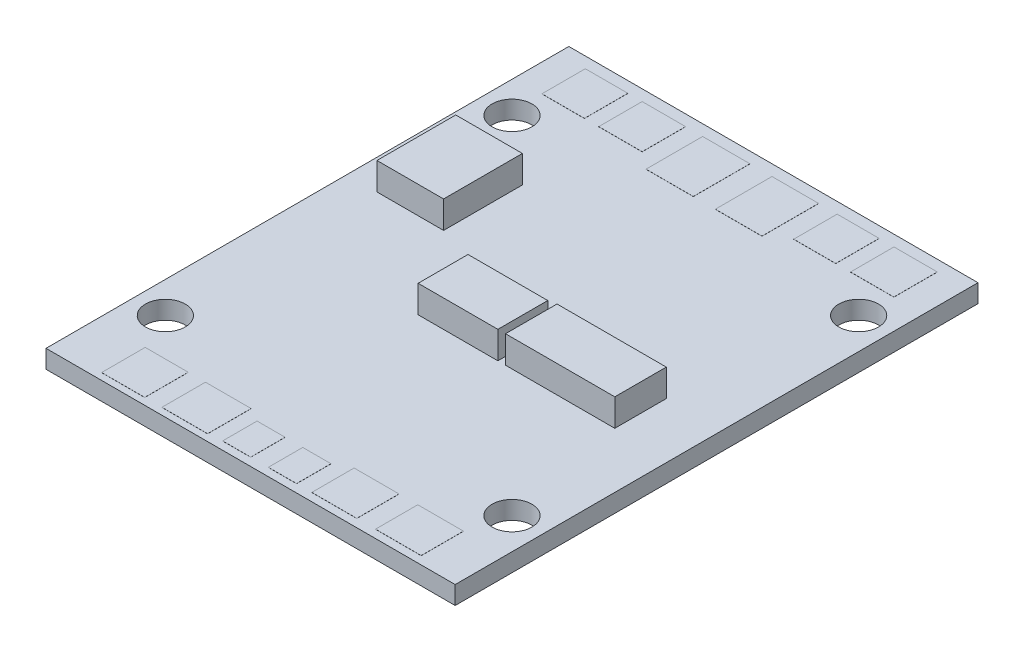
SolidWorks part; units mm, degrees
ref_plane "Front Plane" through (0, 0, 0) normal (0, 0, 1) x (1, 0, 0)
ref_plane "Top Plane" through (0, 0, 0) normal (0, 1, 0) x (1, 0, 0)
ref_plane "Right Plane" through (0, 0, 0) normal (1, 0, 0) x (0, 0, -1)
sketch "Sketch1" plane through (0, 0, 0) normal (0, 1, 0) x (1, 0, 0)
  line L0 (0, 18) -> (0, -18) construction
  line L1 (-18, 23) -> (18, 23)
  line L2 (-18, 23) -> (-18, -23)
  line L3 (-18, -23) -> (18, -23)
  line L4 (18, 23) -> (18, -23)
  line L5 (-18, 23) -> (18, -23) construction
  line L6 (-18, -23) -> (18, 23) construction
  line L7 (18, -18) -> (-18, -18)
  line L8 (18, -18) -> (18, 18)
  line L9 (18, 18) -> (-18, 18)
  line L10 (-18, -18) -> (-18, 18)
  line L11 (18, -18) -> (-18, 18) construction
  line L12 (18, 18) -> (-18, -18) construction
  line L13 (-18, 0) -> (18, 0) construction
  circle A0 centre (-15.25, 15.25) radius 1.75
  circle A1 centre (15.25, 15.25) radius 1.75
  circle A2 centre (-15.25, -15.25) radius 1.75
  circle A3 centre (15.25, -15.25) radius 1.75
  point P0 (0, 0)
  point P6 (0, 0)
  dimension "D3" = 3.5
  dimension "D1" = 46
  dimension "D2" = 36
  dimension "D4" = 30.5
extrude "PCB" add sketch "Sketch1" along normal blind 1.6 contours L9 L4 L1 L2 | L4 L9 L2 L7 A3 A1 A0 A2 | L4 L7 L2 L3 region at (0, 0, -20.5) region at (0, 0, 0) region at (0, 0, 20.5)
sketch "Sketch4" plane through (0, 1.6, 0) normal (0, 1, 0) x (1, 0, 0)
  line L1 (-11.8261, 18.1973) -> (-15.5669, 18.1973)
  line L2 (-11.8261, 18.1973) -> (-11.8261, 22.0181)
  line L3 (-11.8261, 22.0181) -> (-15.5669, 22.0181)
  line L4 (-15.5669, 18.1973) -> (-15.5669, 22.0181)
  line L5 (-10.5658, 22.0181) -> (-6.745, 22.0181)
  line L6 (-10.5658, 22.0181) -> (-10.5658, 18.1973)
  line L7 (-10.5658, 18.1973) -> (-6.745, 18.1973)
  line L8 (-6.745, 22.0181) -> (-6.745, 18.1973)
  line L9 (-5.2447, 22.0181) -> (-1.0838, 22.0181)
  line L10 (-5.2447, 22.0181) -> (-5.2447, 17.0371)
  line L11 (-5.2447, 17.0371) -> (-1.0838, 17.0371)
  line L12 (-1.0838, 22.0181) -> (-1.0838, 17.0371)
  line L13 (0.8566, 22.0181) -> (4.9575, 22.0181)
  line L14 (0.8566, 22.0181) -> (0.8566, 17.0371)
  line L15 (0.8566, 17.0371) -> (4.9575, 17.0371)
  line L16 (4.9575, 22.0181) -> (4.9575, 17.0371)
  line L17 (6.5893, 22.0181) -> (10.285, 22.0181)
  line L18 (6.5893, 22.0181) -> (6.5893, 18.1973)
  line L19 (6.5893, 18.1973) -> (10.285, 18.1973)
  line L20 (10.285, 22.0181) -> (10.285, 18.1973)
  line L21 (11.5882, 22.0181) -> (15.4005, 22.0181)
  line L22 (11.5882, 22.0181) -> (11.5882, 18.1973)
  line L23 (11.5882, 18.1973) -> (15.4005, 18.1973)
  line L24 (15.4005, 22.0181) -> (15.4005, 18.1973)
  line L25 (-13.6965, -22.4064) -> (-9.909, -22.4064)
  line L26 (-13.6965, -22.4064) -> (-13.6965, -18.5756)
  line L27 (-13.6965, -18.5756) -> (-9.909, -18.5756)
  line L28 (-9.909, -22.4064) -> (-9.909, -18.5756)
  line L29 (-8.3953, -22.4064) -> (-4.3777, -22.4064)
  line L30 (-8.3953, -22.4064) -> (-8.3953, -18.5756)
  line L31 (-8.3953, -18.5756) -> (-4.3777, -18.5756)
  line L32 (-4.3777, -22.4064) -> (-4.3777, -18.5756)
  line L33 (-3.1643, -22.2943) -> (-0.6964, -22.2943)
  line L34 (-3.1643, -22.2943) -> (-3.1643, -19.267)
  line L35 (-3.1643, -19.267) -> (-0.6964, -19.267)
  line L36 (-0.6964, -22.2943) -> (-0.6964, -19.267)
  line L37 (0.8566, -22.2943) -> (3.3399, -22.2943)
  line L38 (0.8566, -22.2943) -> (0.8566, -19.267)
  line L39 (0.8566, -19.267) -> (3.3399, -19.267)
  line L40 (3.3399, -22.2943) -> (3.3399, -19.267)
  line L41 (4.6834, -22.2943) -> (8.6372, -22.2943)
  line L42 (4.6834, -22.2943) -> (4.6834, -18.5756)
  line L43 (4.6834, -18.5756) -> (8.6372, -18.5756)
  line L44 (8.6372, -22.2943) -> (8.6372, -18.5756)
  line L45 (10.285, -22.2943) -> (14.3072, -22.2943)
  line L46 (10.285, -22.2943) -> (10.285, -18.5756)
  line L47 (10.285, -18.5756) -> (14.3072, -18.5756)
  line L48 (14.3072, -22.2943) -> (14.3072, -18.5756)
extrude "Pads" add sketch "Sketch4" along normal blind 0.01
sketch "Sketch2" plane through (0, 1.6, 0) normal (0, 1, 0) x (1, 0, 0)
  line L1 (13.118, 0.4566) -> (3.5041, 0.4566)
  line L2 (13.118, 0.4566) -> (13.118, -4.0741)
  line L3 (13.118, -4.0741) -> (3.5041, -4.0741)
  line L4 (3.5041, 0.4566) -> (3.5041, -4.0741)
  line L5 (2.8313, 0.3154) -> (-4.1847, 0.3154)
  line L6 (2.8313, 0.3154) -> (2.8313, -4.0741)
  line L7 (2.8313, -4.0741) -> (-4.1847, -4.0741)
  line L8 (-4.1847, 0.3154) -> (-4.1847, -4.0741)
  line L9 (-15.3548, 10.4054) -> (-9.4909, 10.4054)
  line L10 (-15.3548, 10.4054) -> (-15.3548, 3.472)
  line L11 (-15.3548, 3.472) -> (-9.4909, 3.472)
  line L12 (-9.4909, 10.4054) -> (-9.4909, 3.472)
extrude "Components" add sketch "Sketch2" along normal offset from surface (2.4 mm away) 4 contours L12 L9 L10 L11 | L5 L8 L7 L6 | L1 L4 L3 L2 region at (8.311, 1.6, 1.8087) region at (-0.6767, 1.6, 1.8793) region at (-12.4229, 1.6, -6.9387) up to face at (0, 0, 0)
ref_plane "Wires plane front" through (0, 0, -20) normal (0, 0, -1) x (-1, 0, 0)
ref_plane "Wires plane rear" through (0, 0, 20) normal (0, 0, 1) x (1, 0, 0)
sketch "Wire locations" plane through (0, 0, -20) normal (0, 0, -1) x (-1, 0, 0)
  line L0 (11.8261, 1.6) -> (15.5669, 1.6) construction
  line L1 (6.745, 1.6) -> (10.5658, 1.6) construction
  line L2 (1.0838, 1.6) -> (5.2447, 1.6) construction
  line L3 (11.8261, 1.6) -> (15.5669, 1.6)
  line L4 (6.745, 1.6) -> (10.5658, 1.6)
  line L5 (1.0838, 1.6) -> (5.2447, 1.6)
  line L6 (0, 0) -> (0, 1.6) construction
  line L7 (-15.4005, 1.61) -> (-11.5882, 1.61)
  line L8 (-15.4005, 1.61) -> (-15.4005, 3.11)
  line L9 (-15.4005, 3.11) -> (-11.5882, 3.11)
  line L10 (-11.5882, 1.61) -> (-11.5882, 3.11)
  line L11 (-10.285, 1.6) -> (-6.5893, 1.6)
  line L12 (-10.285, 1.6) -> (-10.285, 3.1)
  line L13 (-10.285, 3.1) -> (-6.5893, 3.1)
  line L14 (-6.5893, 1.6) -> (-6.5893, 3.1)
  line L15 (18, 1.6) -> (-18, 1.6) construction
  line L16 (-15.4005, 1.61) -> (-11.5882, 3.11) construction
  line L17 (-10.285, 1.6) -> (-6.5893, 3.1) construction
  line L18 (-6.5893, 3.1) -> (-6.5218, 3.0683) construction
  line L19 (6.5893, 1.6) -> (6.5893, 3.1)
  line L20 (10.285, 3.1) -> (6.5893, 3.1)
  line L21 (10.285, 1.6) -> (10.285, 3.1)
  line L22 (10.285, 1.6) -> (6.5893, 3.1) construction
  line L23 (10.285, 1.6) -> (6.5893, 1.6)
  line L24 (15.4005, 1.61) -> (11.5882, 3.11) construction
  line L25 (15.4005, 1.61) -> (11.5882, 1.61)
  line L26 (11.5882, 1.61) -> (11.5882, 3.11)
  line L27 (15.4005, 3.11) -> (11.5882, 3.11)
  line L28 (15.4005, 1.61) -> (15.4005, 3.11)
  point P24 (-13.4944, 2.36)
  point P26 (-8.4372, 2.35)
  point P27 (8.4372, 2.35)
  point P32 (13.4944, 2.36)
  dimension "D1" = 1.5
other "POS FL" parameters "Diameter"=1.5, "StubLength"=3
ref_axis "Axis1" through (13.4944, 2.36, -30) along (0, 0, 1)
other "NEG FL" parameters "Diameter"=1.5, "StubLength"=3
ref_axis "Axis2" through (8.4372, 2.35, -30) along (0, 0, 1)
other "POS RL" parameters "Diameter"=1.5, "StubLength"=3
ref_axis "Axis3" through (-8.4372, 2.35, -30) along (0, 0, 1)
other "NEG RL" parameters "Diameter"=1.5, "StubLength"=3
ref_axis "Axis4" through (-13.4944, 2.36, -30) along (0, 0, 1)
